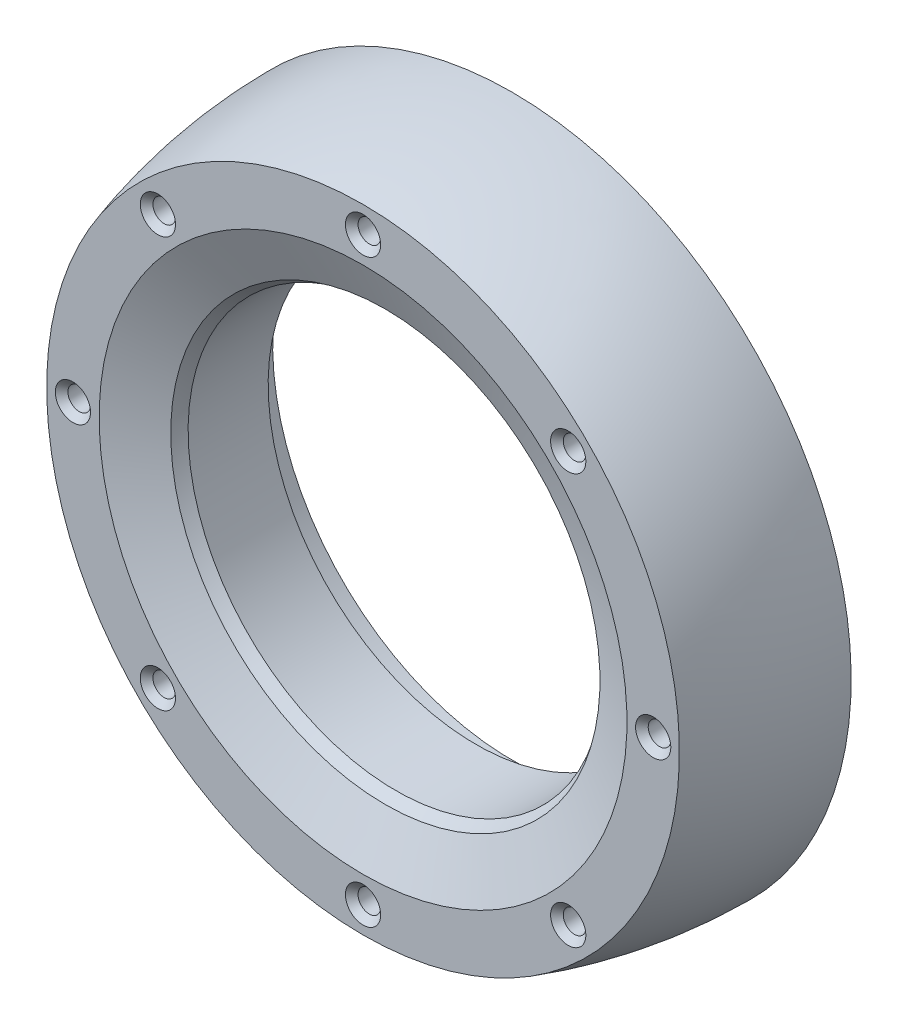
SolidWorks part; units mm, degrees
material "PVC hart"
ref_plane "Ebene vorne" through (0, 0, 0) normal (0, 0, 1) x (1, 0, 0)
ref_plane "Ebene oben" through (0, 0, 0) normal (0, 1, 0) x (1, 0, 0)
ref_plane "Ebene rechts" through (0, 0, 0) normal (1, 0, 0) x (0, 0, -1)
sketch "Skizze1" plane through (0, 0, 0) normal (1, 0, 0) x (0, 0, -1)
  line L0 (0, 26) -> (0, 37.5)
  line L1 (-6, 22.5) -> (-4, 24.5) construction
  line L2 (-16.5, 35) -> (-16.5, 24.906)
  line L3 (-4, 24.5) -> (-4, -24.5) construction
  line L4 (-4, 26) -> (0, 26)
  line L5 (-5.5, 9) -> (-5.5, 22.5) construction
  line L6 (11.0117, 0) -> (-25.0758, 0) construction
  line L7 (0, 26) -> (0, 0) construction
  line L8 (-4, 26) -> (-4, 22.5)
  line L9 (-6, 22.5) -> (-9.0731, 19.4269)
  line L10 (-4, 22.5) -> (-6, 22.5)
  arc A0 (0, 37.5) -> (-16.5, 35) centre (0, -18.2) ccw
  arc A1 (-16.5, 24.906) -> (-9.0731, 19.4269) centre (-22.5, 9) cw
  arc A2 (-9.0731, 19.4269) -> (-5.5, 9) centre (-22.5, 9) cw construction
  dimension "D7" = 17
  dimension "D8" = 5.5
  dimension "D9" = 55.7
  dimension "D1" = 3.5
  dimension "D2" = 135
  dimension "D3" = 75
  dimension "D4" = 33
  dimension "D5" = 70
  dimension "D6" = 18
revolve "Rotation" add sketch "Skizze1" angle 360 about L6
chamfer "Fase1" distance 2.5 angle 45 1 edges at (0, 24.906, 16.5) first distance on face at (0, 19.4269, 9.0731)
sketch "Skizze11" plane through (0, 0, 0) normal (0, 0, -1) x (-1, 0, 0)
  circle A0 centre (0, 0) radius 22.5 construction
  circle A1 centre (0, 0) radius 22.5
extrude "Schnitt-Linear austragen3" cut sketch "Skizze11" against normal through all
sketch "Skizze4" [suppressed] plane through (0, 0, 0) normal (1, 0, 0) x (0, 0, -1)
  line L2 (-4, 23) -> (-4, 26.5)
  line L3 (-4, 26.5) -> (0, 26.5)
  line L4 (-6.2071, 23) -> (-9.4267, 19.7804)
  line L5 (-4, 23) -> (-6.2071, 23)
  line L6 (-6.2071, 23) -> (-9.4267, 19.7804)
  line L7 (-4, 23) -> (-6.2071, 23)
  line L8 (0, 26) -> (0, 37.5) construction
  line L9 (-4, 26) -> (0, 26) construction
  line L10 (0, 26.5) -> (0, 0)
  line L11 (0, 0) -> (-9.4267, 0)
  line L12 (200011.0117, 0) -> (-200025.0758, 0) construction
  line L13 (-9.4267, 0) -> (-9.4267, 19.7804)
  dimension "D2" = 0.5
  dimension "D1" = 0.5
revolve "Druck-Toleranz A" [suppressed] cut sketch "Skizze4" angle 360 about L6
sketch "Skizze5" plane through (0, 0, 0) normal (1, 0, 0) x (0, 0, -1)
  line L0 (-4, 23) -> (-12.8563, 23)
  line L1 (-4, -26) -> (-4, 26) construction
  line L2 (-4, 23) -> (-4, 26.5)
  line L3 (-4, 26.5) -> (0, 26.5)
  line L4 (0, -37.5) -> (0, 37.5) construction
  line L5 (-4, 26) -> (0, 26) construction
  line L6 (-4, 22.5) -> (-6, 22.5) construction
  line L7 (-12.8563, 23) -> (-12.8563, 0)
  line L8 (-12.8563, 0) -> (0, 0)
  line L9 (0, 0) -> (0, 26.5)
  arc A0 (-9.0731, 19.4269) -> (-16.5, 24.906) centre (-22.5, 9) ccw construction
  dimension "D1" = 0.5
  dimension "D2" = 0.5
revolve "Druck-Toleranz I" cut sketch "Skizze5" angle 360 about L6
hole_wizard "Formsenkung für M3 Senkschraube mit Innensechskant1" [suppressed] positions "Skizze6" profile "Skizze7" countersink size "M3" standard "DIN"
sketch "Skizze6" plane through (0, 0, -16.5) normal (0, 0, -1) x (-1, 0, 0)
  line L0 (-22.6968, 22.6968) -> (22.6968, -22.6968) construction
  line L2 (22.6968, 22.6968) -> (-22.6968, -22.6968) construction
  line L4 (-32.0982, 0) -> (32.0982, 0) construction
  line L6 (0, 32.0982) -> (0, -32.0982) construction
  line L8 (0, 35) -> (0, 32.0982)
  line L9 (0, 32.0982) -> (0, 29.1963)
  circle A0 centre (0, 0) radius 32.0982 construction
  point P0 (0, 32.0982)
  point P2 (22.6968, 22.6968)
  point P4 (32.0982, 0)
  point P6 (22.6968, -22.6968)
  point P8 (0, -32.0982)
  point P10 (-22.6968, -22.6968)
  point P12 (-32.0982, 0)
  point P14 (-22.6968, 22.6968)
sketch "Skizze7" plane through (0, 32.0982, -16.5) normal (1, 0, 0) x (0, 1, 0)
  line L0 (0, 0) -> (0, 22.4807)
  line L1 (0, 22.4807) -> (0.8, 22)
  line L2 (0.8, 22) -> (0.8, 1.15)
  line L3 (0.8, 1.15) -> (1.95, 0)
  line L4 (1.95, 0) -> (0, 0)
  line L5 (-0.8, 1.15) -> (-1.95, 0) construction
  line L6 (0, 22.4807) -> (-0.8, 22) construction
  line L7 (0, -6.35) -> (0, 107.95) construction
  dimension "Bohrerdurchmesser" = 1.6
  dimension "Bohrungstiefe" = 22
  dimension "Senkdurchmesser (Oben)" = 3.9
  dimension "Senkwinkel (Oben)" = 90
  dimension "Spitzenwinkel" = 118
hole_wizard "Formsenkung für M3 Senkschraube mit Innensechskant2" positions "Skizze8" profile "Skizze9" countersink size "M3" standard "DIN"
sketch "Skizze8" plane through (0, 0, 16.5) normal (0, 0, 1) x (-1, 0, 0)
  line L0 (-22.6968, 22.6968) -> (22.6968, -22.6968) construction
  line L2 (22.6968, 22.6968) -> (-22.6968, -22.6968) construction
  line L4 (-32.0982, 0) -> (32.0982, 0) construction
  line L6 (0, 32.0982) -> (0, -32.0982) construction
  line L8 (0, 35) -> (0, 32.0982)
  line L9 (0, 32.0982) -> (0, 29.1963)
  circle A0 centre (0, 0) radius 32.0982 construction
  point P0 (0, 32.0982)
  point P2 (22.6968, 22.6968)
  point P4 (32.0982, 0)
  point P6 (22.6968, -22.6968)
  point P8 (0, -32.0982)
  point P10 (-22.6968, -22.6968)
  point P12 (-32.0982, 0)
  point P14 (-22.6968, 22.6968)
  dimension "D1" = 45
sketch "Skizze9" plane through (0, -32.0982, 16.5) normal (1, 0, 0) x (0, -1, 0)
  line L0 (0, 0) -> (0, 22.4807)
  line L1 (0, 22.4807) -> (0.8, 22)
  line L2 (0.8, 22) -> (0.8, 1.15)
  line L3 (0.8, 1.15) -> (1.95, 0)
  line L4 (1.95, 0) -> (0, 0)
  line L5 (-0.8, 1.15) -> (-1.95, 0) construction
  line L6 (0, 22.4807) -> (-0.8, 22) construction
  line L7 (0, -6.35) -> (0, 107.95) construction
  dimension "Bohrerdurchmesser" = 1.6
  dimension "Bohrungstiefe" = 22
  dimension "Senkdurchmesser (Oben)" = 3.9
  dimension "Senkwinkel (Oben)" = 90
  dimension "Spitzenwinkel" = 118
sketch "Skizze10" plane through (0, 0, 0) normal (0, 0, -1) x (-1, 0, 0)
  circle A0 centre (0, 32.0982) radius 1.25
  circle A1 centre (22.6968, 22.6968) radius 1.25
  circle A2 centre (32.0982, 0) radius 1.25
  circle A3 centre (-22.6968, 22.6968) radius 1.25
  circle A4 centre (-32.0982, 0) radius 1.25
  circle A5 centre (-22.6968, -22.6968) radius 1.25
  circle A6 centre (0, -32.0982) radius 1.25
  circle A7 centre (22.6968, -22.6968) radius 1.25
  dimension "D1" = 2.5
extrude "Schnitt-Linear austragen2" cut sketch "Skizze10" against normal through all
